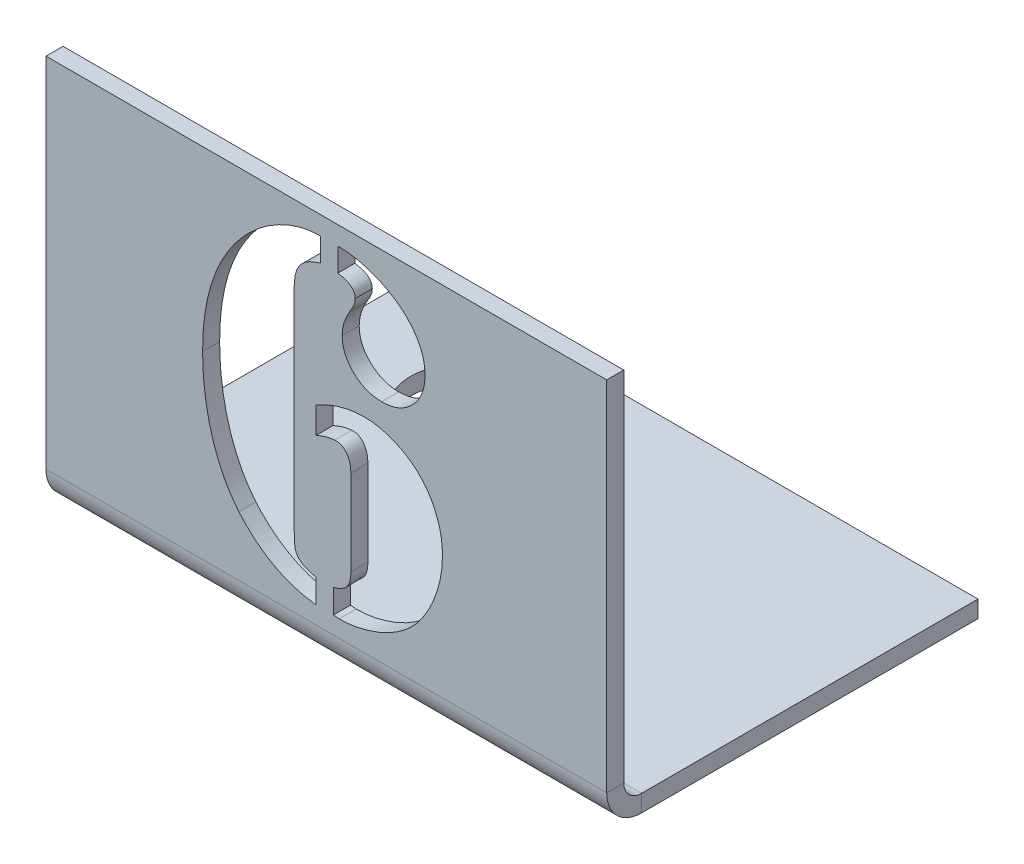
SolidWorks part; units mm, degrees
note: The reader was unsure of these and kept them because the rebuilt part matched: flange length of "Edge-Flange1".
material "16 Ga. SHEET METAL"
ref_plane "Front Plane" through (0, 0, 0) normal (0, 0, 1) x (1, 0, 0)
ref_plane "Top Plane" through (0, 0, 0) normal (0, 1, 0) x (1, 0, 0)
ref_plane "Right Plane" through (0, 0, 0) normal (1, 0, 0) x (0, 0, -1)
sketch "Sketch1" plane through (0, 0, 0) normal (0, 1, 0) x (1, 0, 0)
  line L1 (-25, 0) -> (25, 0)
  line L2 (-25, 0) -> (-25, 30)
  line L3 (-25, 30) -> (25, 30)
  line L4 (25, 0) -> (25, 30)
  dimension "D1" = 30
  dimension "D2" = 50
base flange "Base-Flange1" sketch "Sketch1" thickness 1.5189 reverse thickness direction yes parameters "D1"=1.5875
edge flange "Edge-Flange1" sketch "Sketch8" flange angle 90 flange length 35 flange position bend outside bend radius 1.5875 thickness 1.5189 relief rectangular parameters "D6"=10
sketch "Sketch8" plane through (0, 1.5189, 0) normal (0, 0, 1) x (1, 0, 0)
  line L0 (-25, 0) -> (25, 0) construction
  line L1 (-25, 0) -> (25, 0)
  line L2 (-25, 0) -> (-25, 33.4811)
  line L3 (-25, 33.4811) -> (25, 33.4811)
  line L4 (25, 33.4811) -> (25, 0)
bend "EdgeBend1" bend radius 1.5875 bend angle 90 parameters "D5"=1
hole_wizard "M8 Clearance Hole1" positions "Sketch9" profile "Sketch10" hole size "M8" standard "Peddi DIN" end condition through all
sketch "Sketch9" plane through (0, 1.5189, 0) normal (0, 1, 0) x (1, 0, 0)
  line L0 (25, -3.1064) -> (-25, -3.1064) construction
  line L1 (-25, 30) -> (-25, 0) construction
  point P0 (-13, 21.8936)
  dimension "D1" = 25
  dimension "D2" = 12
sketch "Sketch10" plane through (-13, 1.5189, -21.8936) normal (1, 0, 0) x (0, 0, 1)
  line L0 (0, 0) -> (0, 1.5189)
  line L1 (0, 1.5189) -> (4.5, 1.5189)
  line L2 (4.5, 1.5189) -> (4.5, 0)
  line L5 (4.5, 0) -> (0, 0)
  line L11 (0, -6.35) -> (0, 107.95) construction
  dimension "Thru Hole Dia." = 9
  dimension "Thru Hole Depth" = 1.5189
sketch "Sketch11" plane through (0, 0, 3.1064) normal (0, 0, 1) x (1, 0, 0)
  line L0 (-25, 0) -> (25, 0) construction
  text T0 "6\r\n" font "Stencil" height 28
  dimension "D1" = 5
extrude "Cut-Extrude1" cut sketch "Sketch11" against normal through all
other "Freeze***"
sketch "Bend-Lines1" [suppressed] plane through (0, 0, 0) normal (0, 1, 0) x (1, 0, 0)
sketch "Bounding-Box1" [suppressed] plane through (0, 0, 0) normal (0, 1, 0) x (1, 0, 0)
sheet metal parameters "Sheet-Metal1" thickness 1.5189 parameters "D1"=1.5875
flat pattern "Flat-Pattern1" [suppressed]
sketch "Bend-Lines2" plane through (0, 0, 0) normal (0, 1, 0) x (1, 0, 0)
sketch "Bounding-Box2" [suppressed] plane through (0, 0, 0) normal (0, 1, 0) x (1, 0, 0)
sheet metal parameters "Sheet-Metal2" thickness 1.5189 parameters "D1"=1.5875
flat pattern "Flat-Pattern1" [suppressed]
sketch "Bend-Lines2" plane through (0, 0, 0) normal (0, 1, 0) x (1, 0, 0)
sketch "Bounding-Box2" [suppressed] plane through (0, 0, 0) normal (0, 1, 0) x (1, 0, 0)
bend of the flat pattern "Flatten-<EdgeBend1>1"
sheet metal parameters "Sheet-Metal3" thickness 1.5189 parameters "D1"=1.5875
flat pattern "Flat-Pattern1" [suppressed]
sketch "Bend-Lines2" plane through (0, 0, 0) normal (0, 1, 0) x (1, 0, 0)
sketch "Bounding-Box2" [suppressed] plane through (0, 0, 0) normal (0, 1, 0) x (1, 0, 0)
bend of the flat pattern "Flatten-<EdgeBend1>1"
sheet metal parameters "Sheet-Metal4" thickness 1.5189 parameters "D1"=1.5875
flat pattern "Flat-Pattern1"
sketch "Bend-Lines2" plane through (0, 0, 0) normal (0, -1, 0) x (-1, 0, 0)
  line L0 (-25, -1.724) -> (25, -1.724) construction
  line L1 (-25, -1.724) -> (25, -1.724) construction
sketch3d "Bounding-Box2" [suppressed]
  line L0 (25, -35.3416, 0) -> (25, 30, 0) construction
  line L1 (-25, -35.3416, 0) -> (-25, 30, 0) construction
  line L2 (25, -35.3416, 0) -> (-25, -35.3416, 0) construction
  line L3 (25, 30, 0) -> (-25, 30, 0) construction
bend of the flat pattern "Flatten-<EdgeBend1>1"
